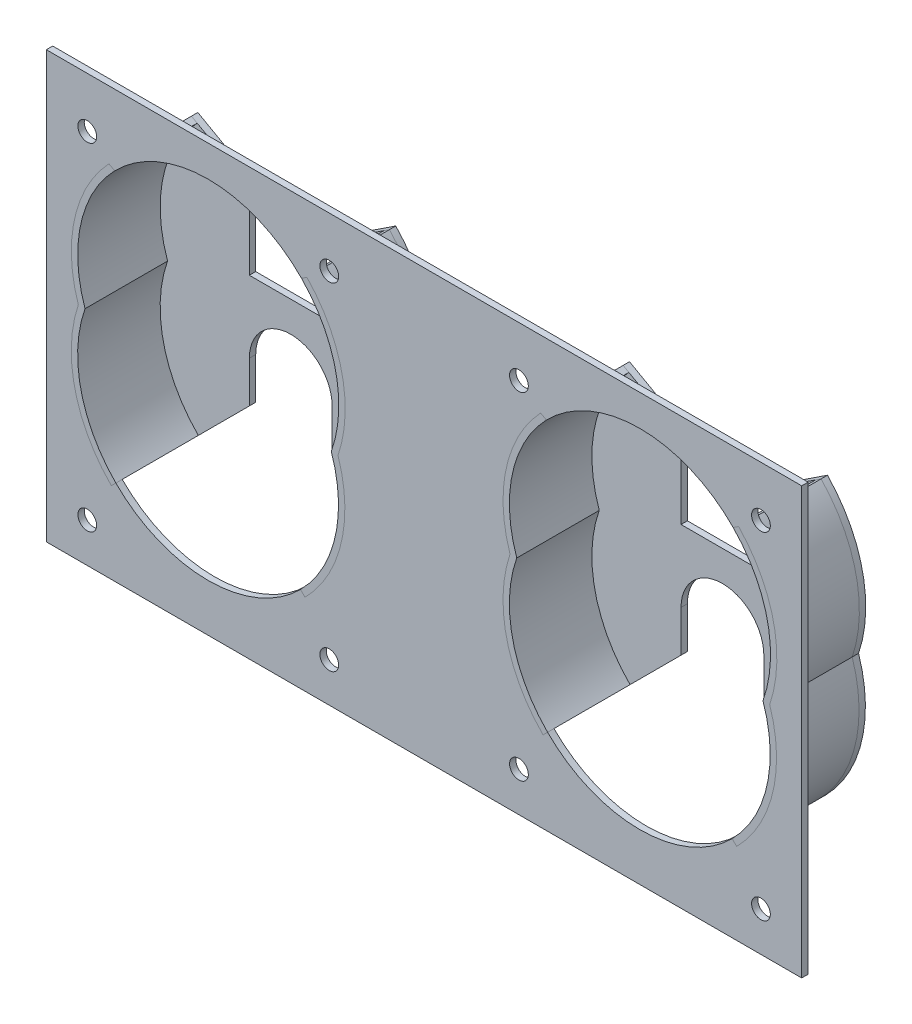
SolidWorks part; units mm, degrees
note: The reader was unsure of these and kept them because the rebuilt part matched: shared geometry of "Sketch1<5>".
ref_plane "Front Plane" through (0, 0, 0) normal (0, 0, 1) x (1, 0, 0)
ref_plane "Top Plane" through (0, 0, 0) normal (0, 1, 0) x (1, 0, 0)
ref_plane "Right Plane" through (0, 0, 0) normal (1, 0, 0) x (0, 0, -1)
sketch "Sketch1" plane through (0, 0, 24.6949) normal (0, 0, -1) x (-1, 0, 0)
  line L0 (-26.7112, -25.9265) -> (-27.4184, -26.6336)
  line L1 (-37.6333, 27.5144) -> (80.981, 27.5144)
  line L2 (-37.6333, 27.5144) -> (-37.6333, -39.4178)
  line L3 (-37.6333, -39.4178) -> (80.981, -39.4178)
  line L4 (80.981, 27.5144) -> (80.981, -39.4178)
  line L7 (-26.0223, -25.2376) -> (-18.7332, -17.9487) construction
  line L8 (2.2718, -25.9541) -> (2.9789, -26.6613)
  line L9 (1.5557, -25.2379) -> (-5.7332, -17.9488) construction
  line L10 (-27.7237, 17.0244) -> (-26.8735, 16.4644)
  line L11 (-26.0218, 15.9034) -> (-19.4679, 11.5863) construction
  line L12 (2.4596, 16.4105) -> (3.3603, 16.9164)
  line L13 (1.5562, 15.9031) -> (-5.5419, 11.9162) construction
  line L14 (40.0613, 17.0243) -> (40.9115, 16.4644)
  line L15 (48.3168, 11.5864) -> (41.7629, 15.9035) construction
  line L16 (70.2442, 16.4103) -> (71.1449, 16.9163)
  line L17 (69.3409, 15.903) -> (62.2428, 11.9161) construction
  line L18 (70.0634, -25.9613) -> (70.7705, -26.6685)
  line L19 (69.3401, -25.238) -> (62.0513, -17.9489) construction
  line L20 (40.3613, -26.6382) -> (41.0685, -25.9312)
  line L21 (41.7621, -25.2375) -> (49.0513, -17.9486) construction
  arc A0 (6.047, -4.6746) -> (-30.4861, -4.7483) centre (-12.2333, 2.1144) ccw
  arc A1 (-30.4861, -4.7483) -> (6.047, -4.6746) centre (-12.2059, -11.4722) ccw
  arc A2 (37.2983, -4.7478) -> (73.8343, -4.6683) centre (55.581, -11.4778) ccw
  arc A3 (73.8343, -4.6683) -> (37.2983, -4.7478) centre (55.5514, 2.114) ccw
  arc A4 (7.1103, -4.6741) -> (2.4596, 16.4105) centre (-12.2333, 2.1144) ccw
  arc A5 (-31.5494, -4.7522) -> (-26.7112, -25.9265) centre (-12.2059, -11.4722) ccw
  arc A6 (74.8976, -4.6674) -> (70.2442, 16.4103) centre (55.5514, 2.114) ccw
  arc A7 (36.2349, -4.7514) -> (41.0685, -25.9312) centre (55.581, -11.4778) ccw
  arc A8 (8.1673, -4.6736) -> (3.3603, 16.9164) centre (-12.2333, 2.1144) ccw
  arc A10 (75.9546, -4.6664) -> (71.1449, 16.9163) centre (55.5514, 2.114) ccw
  arc A12 (-32.6063, -4.756) -> (-27.4184, -26.6336) centre (-12.2059, -11.4722) ccw
  arc A13 (35.178, -4.7551) -> (40.3613, -26.6382) centre (55.581, -11.4778) ccw
  circle A14 centre (-31.2328, 19.6205) radius 1.4732
  circle A15 centre (6.7672, 19.62) radius 1.4732
  circle A16 centre (36.552, 19.6206) radius 1.4732
  circle A17 centre (74.552, 19.6199) radius 1.4732
  circle A18 centre (74.551, -33.2251) radius 1.4732
  circle A19 centre (36.551, -33.2244) radius 1.4732
  circle A20 centre (6.7666, -33.225) radius 1.4732
  circle A21 centre (-31.2334, -33.2245) radius 1.4732
  arc A22 (2.9789, -26.6613) -> (8.1673, -4.6736) centre (-12.2059, -11.4722) ccw
  arc A23 (2.2718, -25.9541) -> (7.1103, -4.6741) centre (-12.2059, -11.4722) ccw
  circle A24 centre (-31.2334, -33.2245) radius 1.4732 construction
  circle A25 centre (36.551, -33.2244) radius 1.4732 construction
  arc A26 (-27.7237, 17.0244) -> (-32.6063, -4.756) centre (-12.2333, 2.1144) ccw
  arc A27 (-26.8735, 16.4644) -> (-31.5494, -4.7522) centre (-12.2333, 2.1144) ccw
  arc A28 (70.7705, -26.6685) -> (75.9546, -4.6664) centre (55.581, -11.4778) ccw
  arc A29 (70.0634, -25.9613) -> (74.8976, -4.6674) centre (55.581, -11.4778) ccw
  arc A30 (40.0613, 17.0243) -> (35.178, -4.7551) centre (55.5514, 2.114) ccw
  arc A31 (40.9115, 16.4644) -> (36.2349, -4.7514) centre (55.5514, 2.114) ccw
  arc A32 (6.5292, -6.1456) -> (-30.9623, -6.2214) centre (-12.2333, 2.1144) ccw
  arc A33 (-30.9729, -3.2789) -> (6.5279, -3.2032) centre (-12.2059, -11.4722) ccw
  arc A34 (74.3172, -6.1388) -> (36.8218, -6.2203) centre (55.5514, 2.114) ccw
  arc A35 (36.8116, -3.2787) -> (74.3145, -3.1971) centre (55.581, -11.4778) ccw
  dimension "D1" = 1
  dimension "D2" = 1
  dimension "D7" = 1
  dimension "D8" = 1
  dimension "D9" = 1
  dimension "D10" = 1
  dimension "D11" = 1
  dimension "D12" = 1
  dimension "D3" = 25.4
  dimension "D4" = 25.4
  dimension "D5" = 25.4
  dimension "D6" = 27.94
extrude "Boss-Extrude1" add sketch "Sketch1" along normal blind 12.954 contours A8 A12 A5 A4 | A10 A13 A7 A6
extrude "Boss-Extrude7" add sketch "Sketch1<5>" along normal blind 1 contours L4 L1 L2 L3 A35 L20 A13 A30 L14 A34 L16 A10 A28 L18 A33 L0 A12 A26 L10 A32 L12 A8 A22 L8 A21 A20 A19 A18 A17 A16 A15 A14
sketch "Sketch1<5>" plane through (0, 0, 24.6949) normal (0, 0, -1) x (-1, 0, 0) same geometry as "Sketch1"
sketch "Sketch4" plane through (0, 0, 11.7409) normal (0, 0, -1) x (-1, 0, 0)
  line L0 (40.3613, -26.6382) -> (49.0513, -17.9486)
  line L1 (41.7621, -25.2375) -> (49.0513, -17.9486) construction
  line L3 (49.0513, 11.1026) -> (49.0513, -0.1736)
  line L5 (62.0513, 11.8085) -> (62.0513, -0.1736)
  line L7 (-18.733, 11.1023) -> (-18.733, -0.1737)
  line L9 (-5.733, 11.8088) -> (-5.733, -0.1738)
  line L10 (40.0613, 17.0243) -> (49.0952, 11.0737)
  line L11 (40.0613, 17.0243) -> (40.9115, 16.4644) construction
  line L12 (71.1449, 16.9163) -> (62.0513, 11.8085)
  line L13 (69.3409, 15.903) -> (62.2428, 11.9161) construction
  line L14 (70.7705, -26.6685) -> (62.0513, -17.9489)
  line L15 (69.3401, -25.238) -> (62.0513, -17.9489) construction
  line L16 (49.0513, -11.4489) -> (49.0513, -17.9486)
  line L17 (49.0513, -0.1736) -> (62.0513, -0.1736)
  line L21 (62.0513, -11.4489) -> (62.0513, -17.9489)
  line L22 (-27.7237, 17.0244) -> (-18.733, 11.1023)
  line L23 (62.0516, -0.1739) -> (49.0516, -0.1736) construction
  line L24 (3.3603, 16.9164) -> (-5.733, 11.8088)
  line L25 (-27.4184, -26.6336) -> (-18.7332, -17.9487)
  line L26 (2.9789, -26.6613) -> (-5.7332, -17.9488)
  line L27 (-26.7112, -25.9265) -> (-27.4184, -26.6336) construction
  line L28 (2.2718, -25.9541) -> (2.9789, -26.6613) construction
  line L29 (-27.7237, 17.0244) -> (-26.8735, 16.4644) construction
  line L30 (2.4596, 16.4105) -> (3.3603, 16.9164) construction
  line L31 (-18.733, -0.1737) -> (-5.733, -0.1738)
  line L32 (-18.7332, -11.4489) -> (-18.7332, -17.9487)
  line L33 (-5.7332, -11.4489) -> (-5.7332, -17.9488)
  arc A0 (8.1673, -4.6736) -> (3.3603, 16.9164) centre (-12.2333, 2.1144) ccw
  arc A1 (-32.6063, -4.756) -> (-27.4184, -26.6336) centre (-12.2059, -11.4722) ccw
  arc A2 (75.9546, -4.6664) -> (35.178, -4.7551) centre (55.5514, 2.114) ccw
  arc A3 (35.178, -4.7551) -> (75.9546, -4.6664) centre (55.581, -11.4778) ccw
  arc A4 (8.1673, -4.6736) -> (3.3603, 16.9164) centre (-12.2333, 2.1144) ccw construction
  arc A5 (2.9789, -26.6613) -> (8.1673, -4.6736) centre (-12.2059, -11.4722) ccw construction
  arc A6 (75.9546, -4.6664) -> (71.1449, 16.9163) centre (55.5514, 2.114) ccw construction
  arc A7 (70.7705, -26.6685) -> (75.9546, -4.6664) centre (55.581, -11.4778) ccw construction
  arc A9 (62.0513, -11.4489) -> (49.0513, -11.4489) centre (55.5513, -11.4489) ccw
  arc A10 (-5.7332, -11.4489) -> (-18.7332, -11.4489) centre (-12.2332, -11.4489) ccw
  arc A13 (2.9789, -26.6613) -> (8.1673, -4.6736) centre (-12.2059, -11.4722) ccw
  arc A14 (-27.7237, 17.0244) -> (-32.6063, -4.756) centre (-12.2333, 2.1144) ccw
extrude "Boss-Extrude8" add sketch "Sketch4" along normal blind 1 contours A9 L21 L14 A3 A2 L12 L5 L17 L3 L10 L0 L16 | A0 L24 L9 L31 L7 L22 A14 A1 L25 L32 A10 L33 L26 A13
